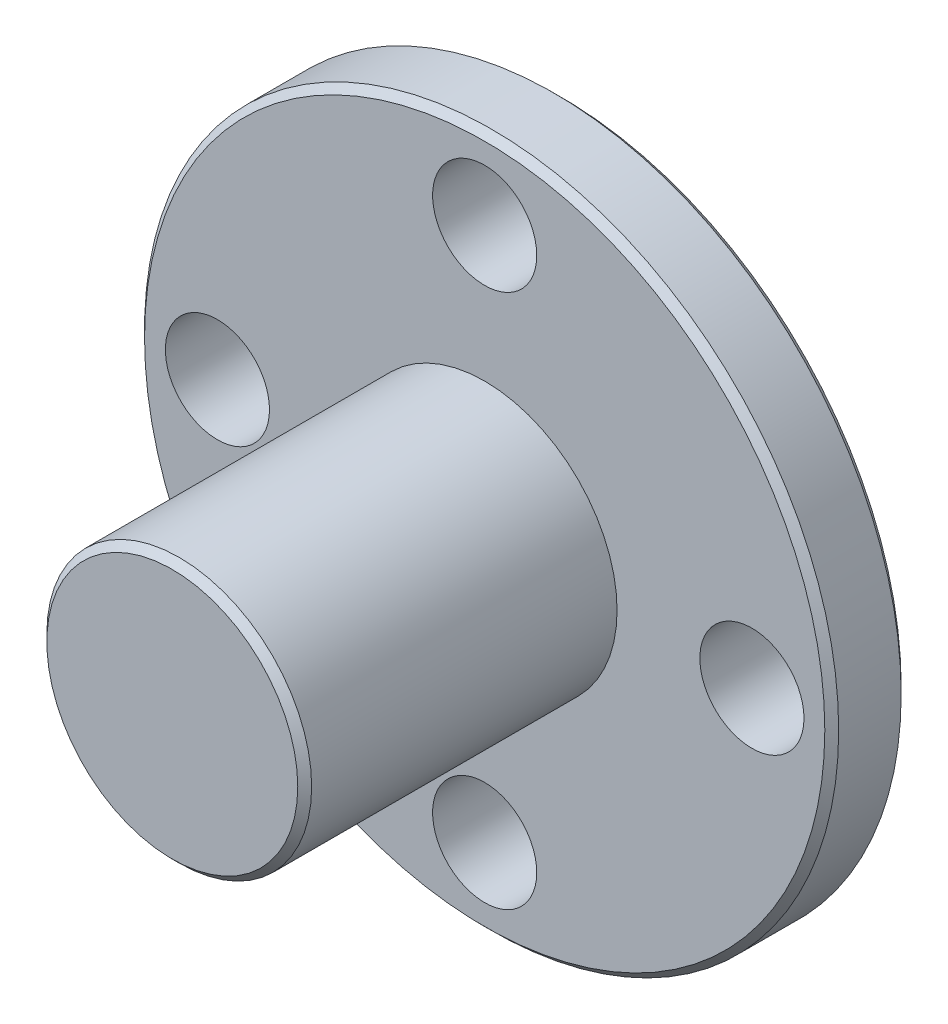
SolidWorks part; units mm, degrees
ref_plane "Front Plane" through (0, 0, 0) normal (0, 0, 1) x (1, 0, 0)
ref_plane "Top Plane" through (0, 0, 0) normal (0, 1, 0) x (1, 0, 0)
ref_plane "Right Plane" through (0, 0, 0) normal (1, 0, 0) x (0, 0, -1)
sketch "Sketch1" plane through (0, 0, 0) normal (0, 0, 1) x (1, 0, 0)
  circle A0 centre (0, 0) radius 10
extrude "Boss-Extrude1" add sketch "Sketch1" along normal blind 2.2
sketch "Sketch2" plane through (0, 0, 2.2) normal (0, 0, 1) x (1, 0, 0)
  line L0 (0, 9.2868) -> (0, -9.2868) construction
  line L1 (-8.6628, 0.7132) -> (11.3372, 0.7132) construction
  circle A0 centre (0, 7.7) radius 1.5
  circle A1 centre (0, 0) radius 3.815
  circle A2 centre (7.7, 0) radius 1.5
  circle A3 centre (0, -7.7) radius 1.5
  circle A4 centre (-7.7, 0) radius 1.5
  point P14 (1.3372, 0.7132)
  dimension "D1" = 7.7
  dimension "D2" = 7.7
  dimension "D3" = 7.7
  dimension "D4" = 7.7
extrude "Cut-Extrude1" cut sketch "Sketch2" against normal through all contours A0 | A2 | A3 | A4
extrude "Boss-Extrude2" add sketch "Sketch2<3>" along normal blind 9 contours A1
sketch "Sketch2<3>" plane through (0, 0, 2.2) normal (0, 0, 1) x (1, 0, 0) same geometry as "Sketch2"
chamfer "Chamfer1" distance 0.2 angle 45 3 edges at (3.815, 0, 11.2) (10, 0, 2.2) (10, 0, 0)
